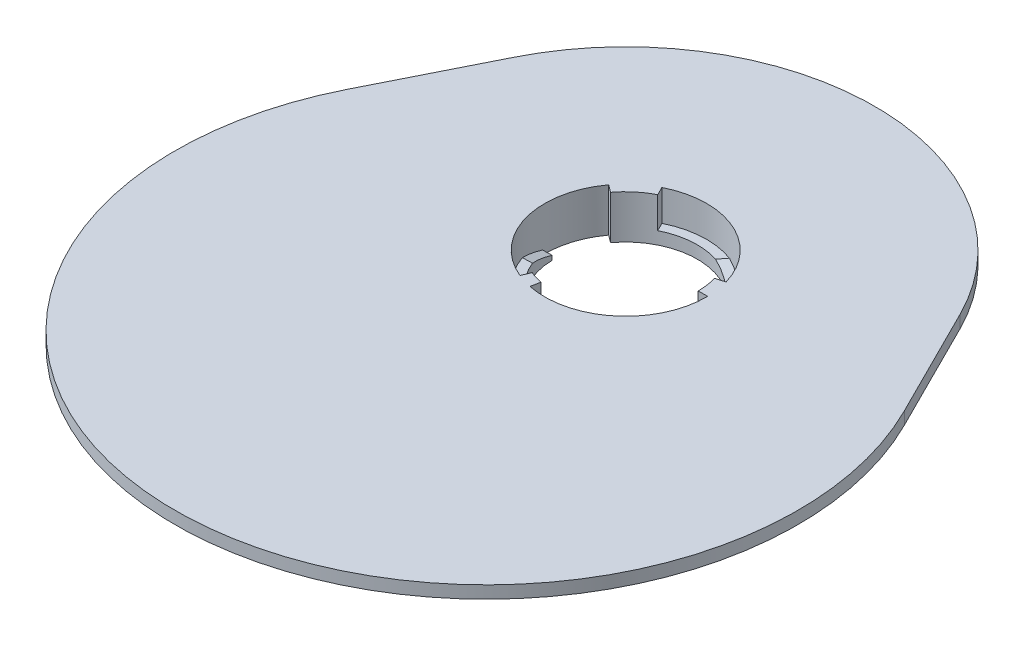
SolidWorks part; units mm, degrees
ref_plane "Front Plane" through (0, 0, 0) normal (0, 0, 1) x (1, 0, 0)
ref_plane "Top Plane" through (0, 0, 0) normal (0, 1, 0) x (1, 0, 0)
ref_plane "Right Plane" through (0, 0, 0) normal (1, 0, 0) x (0, 0, -1)
sketch "Sketch1" plane through (0, 0, 0) normal (0, 1, 0) x (1, 0, 0)
  line L0 (-35.7771, 17.8885) -> (-44.7214, 0)
  line L2 (35.7771, 17.8885) -> (44.7214, 0)
  arc A0 (-35.7771, 17.8885) -> (35.7771, 17.8885) centre (0, 0) cw
  arc A1 (-44.7214, 0) -> (44.7214, 0) centre (0, -22.3607) ccw
  circle A2 centre (0, 0) radius 13
  dimension "D1" = 50
  dimension "D3" = 40
  dimension "D4" = 26
  dimension "D2" = 20
extrude "Boss-Extrude1" add sketch "Sketch1" along normal blind 2
sketch "Sketch3" plane through (0, 0, 0) normal (0, -1, 0) x (1, 0, 0)
  circle A0 centre (0, 0) radius 20
  circle A1 centre (0, 0) radius 13
  circle A2 centre (0, 0) radius 13 construction
  dimension "D1" = 40
extrude "Boss-Extrude2" add sketch "Sketch3" along normal blind 5
chamfer "Chamfer1" distance 3 angle 45 1 edges at (0, -5, -20)
sketch "Sketch6" plane through (0, -5, 0) normal (0, -1, 0) x (1, 0, 0)
  line L0 (0, 0) -> (-5.1437, -10.2855)
  line L1 (0, 0) -> (-11.4957, 0.3149) construction
  line L2 (0, 0) -> (-9.2526, -6.8293) construction
  line L3 (0, 0) -> (-3.556, -10.9364) construction
  line L4 (0, 0) -> (-12.9951, 0.356)
  line L5 (0, 0) -> (-10.4595, -7.7201)
  line L6 (0, 0) -> (-2.6521, 12.7266)
  line L7 (0, 0) -> (5.4382, 11.8079)
  line L8 (0, 0) -> (12.482, -3.6332)
  line L9 (0, 0) -> (7.9912, -10.2538)
  line L10 (0, 0) -> (-4.9604, 12.0164)
  line L11 (0, 0) -> (12.9989, -0.1654)
  line L12 (-5.1437, -10.2855) -> (-5.8146, -11.6271)
  line L13 (-2.6521, 12.7266) -> (5.4382, 11.8079) construction
  line L14 (5.4382, 11.8079) -> (12.9989, -0.1654) construction
  line L15 (12.9989, -0.1654) -> (12.482, -3.6332) construction
  line L16 (12.482, -3.6332) -> (7.9912, -10.2538) construction
  line L17 (7.9912, -10.2538) -> (-5.8146, -11.6271) construction
  line L18 (-5.8146, -11.6271) -> (-10.4595, -7.7201) construction
  line L19 (-10.4595, -7.7201) -> (-12.9951, 0.356) construction
  line L20 (-4.9604, 12.0164) -> (-12.9951, 0.356) construction
  line L21 (-2.6521, 12.7266) -> (-4.9604, 12.0164) construction
  line L22 (-3.556, -10.9364) -> (-5.8146, -11.6271) construction
  circle A0 centre (0, 0) radius 10.75
  circle A1 centre (0, 0) radius 11.5
  circle A2 centre (0, 0) radius 13
  circle A3 centre (0, 0) radius 13 construction
  point P7 (0, 0)
  circle M16 centre (0, 0) radius 13
  dimension "D9" = 26
  dimension "D1" = 8.1423
  dimension "D2" = 14.1606
  dimension "D3" = 3.5061
  dimension "D4" = 8
  dimension "D5" = 13.874
  dimension "D6" = 6.0696
  dimension "D7" = 8.4648
  dimension "D8" = 14.1606
  dimension "D10" = 2.3619
  dimension "D11" = 1.5
  dimension "D12" = 0.75
extrude "Boss-Extrude4" add sketch "Sketch6" against normal blind 2 contours A1 L12 L9 M16 | A1 L5 L12 M16 | A1 L10 L4 M16 | A1 L6 L10 M16 | A1 L11 L7 M16 | A1 L8 L11 M16 region at (1.151, -5, -11.5707) region at (-7.8225, -5, -9.2996) region at (-9.5506, -5, 6.5809) region at (-3.6015, -5, 11.7061) region at (9.8067, -5, 6.1927) region at (12.0943, -5, -1.8029)
extrude "Boss-Extrude5" add sketch "Sketch6<4>" against normal up to surface (7 mm away) contours A1 L5 L12 M16 | A1 L6 L10 M16 | A1 L8 L11 M16 region at (-7.8225, -5, -9.2996) region at (-3.6015, -5, 11.7061) region at (12.0943, -5, -1.8029) up to face at (0, 2, 3.618)
sketch "Sketch6<4>" plane through (0, -5, 0) normal (0, -1, 0) x (1, 0, 0) same geometry as "Sketch6"
chamfer "Chamfer2" distance 1.3 angle 72 3 edges at (5.1245, -3, 11.1267) (-12.2454, -3, 0.3355) (7.5302, -3, -9.6622) first distance on face at (5.1245, -4, 11.1267) first distance on face at (-12.2454, -4, 0.3355) first distance on face at (7.5302, -4, -9.6622)
